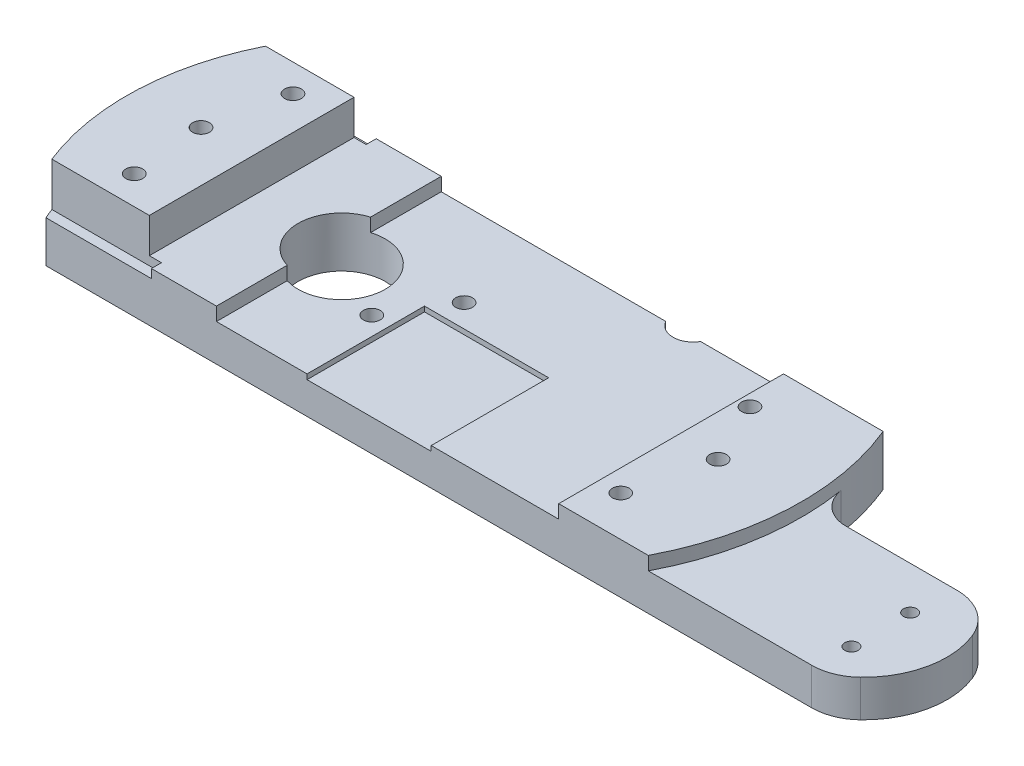
SolidWorks part; units mm, degrees
ref_plane "Front Plane" through (0, 0, 0) normal (0, 0, 1) x (1, 0, 0)
ref_plane "Top Plane" through (0, 0, 0) normal (0, 1, 0) x (1, 0, 0)
ref_plane "Right Plane" through (0, 0, 0) normal (1, 0, 0) x (0, 0, -1)
sketch "Sketch1" plane through (0, 0, 0) normal (0, 1, 0) x (1, 0, 0)
  line L1 (-97.5, -33.5) -> (97.5, -33.5)
  line L2 (-97.5, -33.5) -> (-97.5, 33.5)
  line L3 (-97.5, 33.5) -> (97.5, 33.5)
  line L4 (97.5, -33.5) -> (97.5, 33.5)
  line L5 (-97.5, -33.5) -> (97.5, 33.5) construction
  line L6 (-97.5, 33.5) -> (97.5, -33.5) construction
  point P0 (0, 0)
  dimension "D1" = 67
  dimension "D2" = 195
extrude "Boss-Extrude1" add sketch "Sketch1" along normal blind 25.4
sketch "Sketch2" plane through (0, 0, 0) normal (0, -1, 0) x (1, 0, 0)
  line L0 (-97.5, -33.5) -> (-97.5, 33.5) construction
  line L1 (97.5, 33.5) -> (97.5, -33.5) construction
  line L2 (97.5, 33.5) -> (88.5, 33.5)
  line L3 (-97.5, 33.5) -> (97.5, 33.5) construction
  line L4 (97.5, -33.5) -> (91.5, -33.5)
  line L5 (97.5, -33.5) -> (-97.5, -33.5) construction
  line L6 (-97.5, 33.5) -> (-91, 33.5)
  line L7 (-97.5, -33.5) -> (-88, -33.5)
  circle A0 centre (18.0922, -3.2198) radius 79.4078
  circle A1 centre (-22.6589, 2.9929) radius 74.8411
  line M7 (97.5, -33.5) -> (97.5, 33.5)
  line M8 (97.5, 33.5) -> (-97.5, 33.5)
  line M9 (-97.5, 33.5) -> (-97.5, -33.5)
  line M10 (-97.5, -33.5) -> (97.5, -33.5)
  dimension "D1" = 9
  dimension "D2" = 6
  dimension "D3" = 6.5
  dimension "D4" = 9.5
extrude "Cut-Extrude1" cut sketch "Sketch2" against normal through all contours A0 M7 M8 | A0 M10 M7 | A1 M9 M10 | A1 M8 M9 region at (94.8284, 0, 24.4273) region at (95.7123, 0, -25.9883) region at (-95.5654, 0, 25.941) region at (-94.6839, 0, -24.4966)
sketch "Sketch3" plane through (0, 0, 33.5) normal (0, 0, -1) x (-1, 0, 0)
  line L0 (97.5, 25.4) -> (63.2, 25.4)
  line L2 (63.2, 25.4) -> (63.2, 15)
  line L3 (63.2, 15) -> (40.2, 15)
  line L4 (40.2, 15) -> (40.2, 11)
  line L5 (40.2, 11) -> (-61.8, 11)
  line L6 (-91.5, 25.4) -> (88, 25.4) construction
  line L10 (97.5, 0) -> (97.5, 25.4) construction
  line L11 (-61.8, 11) -> (-61.8, 15)
  line L12 (-61.8, 15) -> (-97.5, 15)
  line L13 (-97.5, 25.4) -> (-97.5, 0) construction
  line L14 (-97.5, 15) -> (-97.5, 25.4)
  line L15 (-97.5, 25.4) -> (63.2, 25.4)
  line M13 (-88.5, 0) -> (-88.5, 25.4)
  line M14 (-88.5, 25.4) -> (91, 25.4)
  dimension "D1" = 10.4
  dimension "D2" = 34.3
  dimension "D3" = 23
  dimension "D4" = 4
  dimension "D5" = 102
extrude "Cut-Extrude2" cut sketch "Sketch3" along normal through all contours L11 L12 L2 L3 L4 L5 M13 M14 | L2 L3 L4 L5 L11 L12 L14 L15 region at (12.2699, 18.7206, 33.5)
sketch "Sketch4" plane through (0, 25.4, 0) normal (0, 1, 0) x (1, 0, 0)
  line L0 (-59.5873, 33.5) -> (-59.5873, 30.5)
  line L1 (-63.2, 33.5) -> (-88, 33.5) construction
  line L2 (-59.5873, 30.5) -> (-89.5873, 30.5)
  line L3 (-59.5873, -33.5) -> (-59.5873, -30.5)
  line L4 (-91, -33.5) -> (-63.2, -33.5) construction
  line L5 (-59.5873, -30.5) -> (-92.2617, -30.5)
  line L6 (-59.5873, 33.5) -> (-63.2, 33.5)
  line L7 (-59.5873, -33.5) -> (-63.2, -33.5)
  arc A0 (-88, 33.5) -> (-91, -33.5) centre (-22.6589, -2.9929) ccw construction
  line M5 (-91, -33.5) -> (-63.2, -33.5)
  line M6 (-63.2, -33.5) -> (-63.2, 33.5)
  line M7 (-63.2, 33.5) -> (-88, 33.5)
  arc M8 (-88, 33.5) -> (-91, -33.5) centre (-22.6589, -2.9929) ccw
  dimension "D1" = 3
  dimension "D2" = 3
  dimension "D3" = 30
extrude "Cut-Extrude3" cut sketch "Sketch4" against normal blind 13 contours L2 M6 M7 M8 | L0 L6 L2 M6 | L5 M6 M8 M5 | L7 L3 L5 M6 region at (-61.3937, 25.4, -32) region at (-76.0082, 25.4, -31.9845) region at (-77.4242, 25.4, 31.9889) region at (-61.3937, 25.4, 32)
sketch "Sketch6" plane through (0, 0, 0) normal (0, -1, 0) x (1, 0, 0)
  line L0 (-63.2, -33.5) -> (-97.5, -33.5)
  line L1 (91.5, -33.5) -> (-88, -33.5) construction
  line L2 (-63.2, -33.5) -> (-63.2, 33.5)
  line L3 (-91, 33.5) -> (88.5, 33.5) construction
  line L4 (-63.2, -9) -> (-28.1, -9) construction
  line L5 (-63.2, 8.7) -> (-18.7, 8.7) construction
  line L6 (-63.2, -8.3) -> (-8.2, -8.3) construction
  line L8 (91.5, -33.5) -> (-88, -33.5) construction
  line L9 (-97.5, -33.5) -> (-97.5, 33.5)
  line L10 (-97.5, 33.5) -> (-63.2, 33.5)
  circle A1 centre (-18.7, 8.7) radius 2.5
  circle A2 centre (74.1, -1.7) radius 2.5
  circle A3 centre (68.3, 21.5) radius 2.5
  circle A4 centre (65.3, -20) radius 2.5
  circle A5 centre (-8.2, -8.3) radius 2.5
  circle A6 centre (-76.2, 22) radius 2.5
  circle A7 centre (-78.2, 0.1) radius 2.5
  circle A8 centre (-73.2, -22.3) radius 2.5
  arc A10 (-91, 33.5) -> (-88, -33.5) centre (-22.6589, 2.9929) ccw construction
  dimension "D22" = 5
  dimension "D3" = 35.1
  dimension "D4" = 34.3
  dimension "D5" = 44.5
  dimension "D6" = 24.5
  dimension "D7" = 55
  dimension "D8" = 42.2
  dimension "D9" = 137.3
  dimension "D10" = 128.5
  dimension "D11" = 131.5
  dimension "D12" = 10
  dimension "D13" = 15
  dimension "D14" = 13
  dimension "D15" = 11.2
  dimension "D16" = 33.6
  dimension "D17" = 55.5
  dimension "D18" = 31.8
  dimension "D19" = 55
  dimension "D20" = 13.5
  dimension "D21" = 25.2
extrude "Cut-Extrude4" cut sketch "Sketch6" against normal through all contours A5 | A1 | A6 | A7 | A8 | A4 | A2 | A3 region at (-18.7, 0, 8.7) region at (74.1, 0, -1.7) region at (68.3, 0, 21.5) region at (65.3, 0, -20) region at (-8.2, 0, -8.3) region at (-76.2, 0, 22) region at (-78.2, 0, 0.1) region at (-73.2, 0, -22.3)
sketch "Sketch7" plane through (0, 11, 0) normal (0, 1, 0) x (1, 0, 0)
  line L1 (-13.2, 1.5) -> (23.8, 1.5)
  line L2 (-13.2, 1.5) -> (-13.2, -33.5)
  line L3 (-13.2, -33.5) -> (23.8, -33.5)
  line L4 (23.8, 1.5) -> (23.8, -33.5)
  line L8 (-63.2, 30.5) -> (-63.2, -30.5) construction
  line L9 (-63.2, 30.5) -> (-63.2, -30.5) construction
  line L10 (-40.2, -33.5) -> (61.8, -33.5) construction
  dimension "D1" = 50
  dimension "D2" = 87
  dimension "D3" = 35
extrude "Cut-Extrude5" cut sketch "Sketch7" against normal blind 1.5
sketch "Sketch8" plane through (0, 25.4, 0) normal (0, 1, 0) x (1, 0, 0)
  line L0 (-59.5873, -33.5) -> (-97.5, -33.5)
  line L1 (-97.5, -33.5) -> (-97.5, 33.5)
  line L3 (-97.5, 33.5) -> (31.9, 33.5)
  line L6 (31.9, 36.5) -> (31.9, 30.5)
  line L7 (31.9, 33.5) -> (37.0962, 33.5)
  line L10 (-59.5873, 33.5) -> (-88, 33.5) construction
  line L11 (-40.2, 33.5) -> (61.8, 33.5) construction
  circle A1 centre (31.9, 36.5) radius 6
  arc A2 (-89.5873, 30.5) -> (-92.2617, -30.5) centre (-22.6589, -2.9929) ccw construction
  dimension "D1" = 12
  dimension "D2" = 129.4
extrude "Cut-Extrude6" cut sketch "Sketch8" against normal blind 18.5 contours L6 A1 L7 | L3 A1 L6 region at (29.8648, 25.4, -32.2699) region at (33.9352, 25.4, -32.2699)
sketch "Sketch9" plane through (0, 0, 0) normal (0, -1, 0) x (1, 0, 0)
  line L0 (88.5, 33.5) -> (137.2004, 33.5)
  line L1 (139.5727, -7.5) -> (97.3846, -7.5)
  arc A0 (153.4738, 1.8643) -> (147.5429, 29.3643) centre (130.3054, 11.2571) ccw
  arc A1 (91.5, -33.5) -> (88.5, 33.5) centre (18.0922, -3.2198) ccw construction
  arc A2 (143.371, -10.0569) -> (147.5429, 29.3643) centre (130.3054, 11.2571) ccw construction
  arc A3 (147.5429, 29.3643) -> (137.2004, 33.5) centre (137.2004, 18.5) ccw
  arc A4 (147.5429, 29.3643) -> (138.7351, 33.4213) centre (137.2004, 18.5) ccw construction
  arc A5 (139.5727, -7.5) -> (153.4738, 1.8643) centre (139.5727, 7.5) ccw
  circle A6 centre (114.5043, -27.5) radius 16 construction
  circle A7 centre (104.9862, 59.4808) radius 16 construction
  circle A8 centre (114.5043, -27.5) radius 20 construction
  arc A9 (97.3846, -7.5) -> (88.5, 33.5) centre (18.0922, -3.2198) ccw
  circle A10 centre (138.3, 5.25) radius 2
  circle A11 centre (138.3, 22.75) radius 2
  circle A12 centre (138.3, 22.75) radius 2 construction
  circle A13 centre (138.3, 5.25) radius 2 construction
  dimension "D1" = 4
extrude "Boss-Extrude2" add sketch "Sketch9" against normal up to surface (11 mm away) up to face at (-16.2, 11, 8.7)
fillet "Fillet1" radius 10 1 edges at (97.3846, 5.5, -7.5)
sketch "Sketch10" plane through (0, -3, 0) normal (0, -1, 0) x (1, 0, 0)
  circle A0 centre (-36.3824, 0) radius 13
  dimension "D1" = 26
extrude "Cut-Extrude7" cut sketch "Sketch10" against normal up to surface (18 mm away) up to face at (-55.6437, 15, 0)
